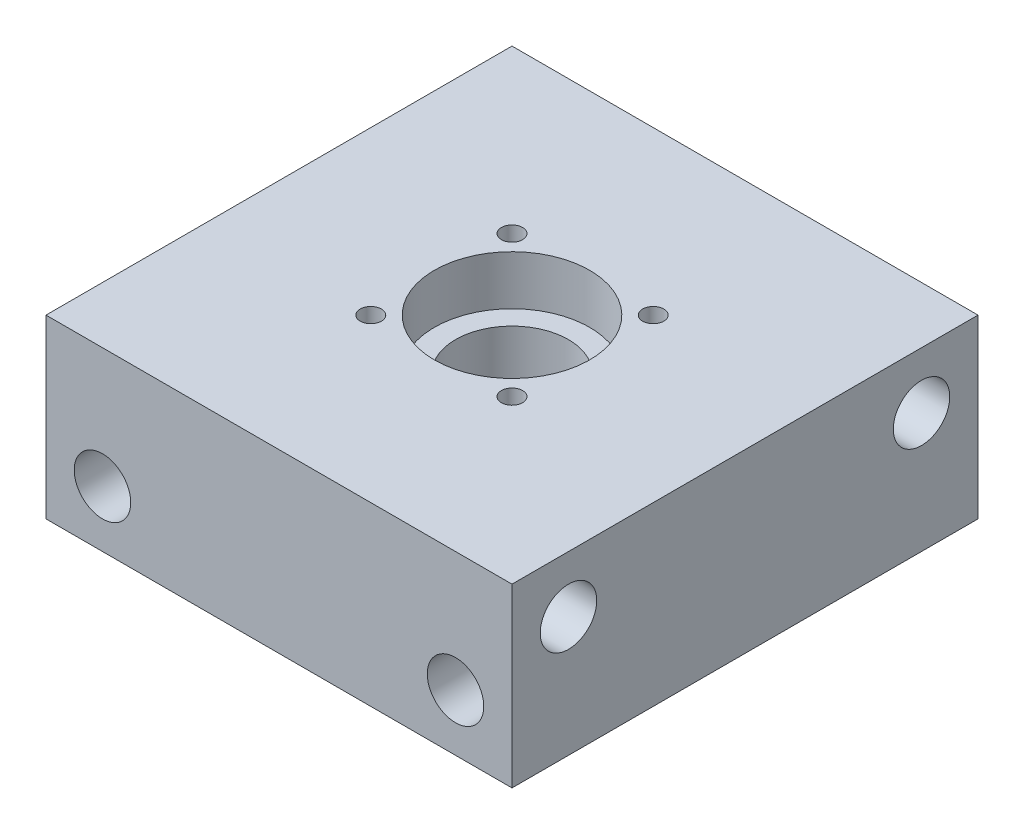
SolidWorks part; units mm, degrees
material "ABS"
ref_plane "Front Plane" through (0, 0, 0) normal (0, 0, 1) x (1, 0, 0)
ref_plane "Top Plane" through (0, 0, 0) normal (0, 1, 0) x (1, 0, 0)
ref_plane "Right Plane" through (0, 0, 0) normal (1, 0, 0) x (0, 0, -1)
sketch "Sketch1" plane through (0, 0, 0) normal (0, 1, 0) x (1, 0, 0)
  line L0 (-25, 94.322) -> (-25, -161.1056) construction
  line L1 (0, 212.1837) -> (0, -209.6879) construction
  line L2 (-178.557, 25) -> (189.3494, 25) construction
  line L3 (-284.8586, 0) -> (271.277, 0) construction
  line L4 (-33, 29) -> (33, 29)
  line L5 (-29, 33) -> (-21, 33)
  line L6 (-29, 33) -> (-29, -33)
  line L7 (-29, -33) -> (-21, -33)
  line L8 (-21, 33) -> (-21, -33)
  line L9 (-33, 21) -> (33, 21)
  line L10 (-33, -29) -> (-33, -21)
  line L11 (-178.557, -25) -> (189.3494, -25) construction
  line L12 (33, -29) -> (33, -21)
  line L13 (-33, 29) -> (33, 29)
  line L14 (-33, 29) -> (-33, 21)
  line L15 (-33, 21) -> (33, 21)
  line L16 (33, 29) -> (33, 21)
  line L17 (-33, -21) -> (33, -21)
  line L18 (-33, -29) -> (33, -29)
  line L19 (-33, -21) -> (33, -21)
  line L20 (-33, -29) -> (33, -29)
  line L21 (29, -33) -> (21, -33)
  line L22 (29, 33) -> (21, 33)
  line L23 (25, 94.322) -> (25, -161.1056) construction
  line L24 (21, 33) -> (21, -33)
  line L25 (29, 33) -> (29, -33)
  line L26 (13.2332, 10) -> (11.6166, 12.8)
  line L27 (-33, 33) -> (33, 33)
  line L28 (-33, 33) -> (-33, -33)
  line L29 (-33, -33) -> (33, -33)
  line L30 (33, 33) -> (33, -33)
  line L31 (-6.7668, 10) -> (-8.3834, 12.8)
  line L32 (-8.3834, 12.8) -> (-11.6166, 12.8)
  line L33 (-11.6166, 12.8) -> (-13.2332, 10)
  line L34 (-13.2332, 10) -> (-11.6166, 7.2)
  line L35 (-11.6166, 7.2) -> (-8.3834, 7.2)
  line L36 (-8.3834, 7.2) -> (-6.7668, 10)
  line L37 (11.6166, 12.8) -> (8.3834, 12.8)
  line L38 (8.3834, 12.8) -> (6.7668, 10)
  line L39 (6.7668, 10) -> (8.3834, 7.2)
  line L40 (8.3834, 7.2) -> (11.6166, 7.2)
  line L41 (11.6166, 7.2) -> (13.2332, 10)
  line L42 (13.2332, -10) -> (11.6166, -7.2)
  line L43 (11.6166, -7.2) -> (8.3834, -7.2)
  line L44 (8.3834, -7.2) -> (6.7668, -10)
  line L45 (6.7668, -10) -> (8.3834, -12.8)
  line L46 (8.3834, -12.8) -> (11.6166, -12.8)
  line L47 (11.6166, -12.8) -> (13.2332, -10)
  line L48 (-6.7668, -10) -> (-8.3834, -7.2)
  line L49 (-8.3834, -7.2) -> (-11.6166, -7.2)
  line L50 (-11.6166, -7.2) -> (-13.2332, -10)
  line L51 (-13.2332, -10) -> (-11.6166, -12.8)
  line L52 (-11.6166, -12.8) -> (-8.3834, -12.8)
  line L53 (-8.3834, -12.8) -> (-6.7668, -10)
  circle A0 centre (0, 0) radius 11
  circle A1 centre (0, 0) radius 8
  circle A2 centre (-10, 10) radius 1.5
  circle A3 centre (10, 10) radius 1.5
  circle A4 centre (10, 10) radius 2.8 construction
  circle A5 centre (10, -10) radius 1.5
  circle A6 centre (-10, 10) radius 2.8 construction
  circle A7 centre (10, -10) radius 2.8 construction
  circle A8 centre (-10, -10) radius 1.5
  circle A9 centre (-10, -10) radius 2.8 construction
  dimension "D5" = 2
  dimension "D6" = 2
  dimension "D7" = 3
  dimension "D14" = 5.6
  dimension "D2" = 25
  dimension "D3" = 25
  dimension "D4" = 4
  dimension "D8" = 10
  dimension "D9" = 10
  dimension "D12" = 8
  dimension "D13" = 4
extrude "Boss-Extrude1" add sketch "Sketch1" along normal blind 25 contours L24 L9 L8 L17 A3 A2 A0 | L24 L4 L8 L9 | L6 L9 L8 L4 | L27 L8 L4 L24 | L8 L5 L6 L4 | L27 L28 L4 L6 | L4 L14 L9 L6 | L9 L28 L17 L6 | L6 L17 L8 L9 | L6 L18 L8 L17 | L10 L18 L6 L17 | L28 L29 L6 L18 | L18 L6 L7 L8 | L24 L17 L8 L18 | L8 L29 L24 L18 | L25 L20 L24 L21 | L25 L19 L24 L20 | L17 L25 L18 L12 | L30 L18 L25 L29 | L25 L15 L24 L19 | L30 L9 L25 L17 | L25 L13 L24 L15 | L4 L25 L9 L16 | L25 L22 L24 L13 | L30 L27 L25 L4 | L35 L36 L31 L32 L33 L34 A2 | L40 L41 L26 L37 L38 L39 A3 | L46 L47 L42 L43 L44 L45 A5 | L52 L53 L48 L49 L50 L51 A8 region at (-31, 0, -31) region at (-31, 0, -25) region at (-25, 0, -31) region at (-25, 0, -25) region at (-31, 0, 0) region at (0, 0, -31) region at (0, 0, -25) region at (-25, 0, 0) region at (-31, 0, 25) region at (25, 0, -31) region at (25, 0, -25) region at (0, 0, -20.406) region at (-25, 0, 25) region at (-31, 0, 31) region at (31, 0, -31) region at (31, 0, -25) region at (25, 0, 0) region at (0, 0, 25) region at (-25, 0, 31) region at (31, 0, 0) region at (25, 0, 25) region at (0, 0, 31) region at (31, 0, 25) region at (25, 0, 31) region at (31, 0, 31) region at (12.3508, 0, -8.6428) region at (-7.6492, 0, -8.6428) region at (12.3508, 0, 11.3572) region at (-7.6492, 0, 11.3572)
extrude "Boss-Extrude2" add sketch "Sketch1<4>" along normal blind 18 contours A0 A1 region at (-10.6889, 0, 0)
sketch "Sketch1<4>" plane through (0, 0, 0) normal (0, 1, 0) x (1, 0, 0) same geometry as "Sketch1"
sketch "Sketch2" plane through (-33, 0, 0) normal (-1, 0, 0) x (0, 0, 1)
  line L0 (0, 0) -> (0, 25) construction
  line L1 (-33, 25) -> (33, 25) construction
  circle A0 centre (-25, 17) radius 4
  circle A1 centre (25, 17) radius 4
  dimension "D3" = 8
  dimension "D1" = 25
  dimension "D2" = 8
extrude "Cut-Extrude1" cut sketch "Sketch2" against normal through all
sketch "Sketch3" plane through (0, 0, -33) normal (0, 0, -1) x (-1, 0, 0)
  line L0 (0, 0) -> (0, 25) construction
  line L1 (33, 25) -> (-33, 25) construction
  line L2 (33, 0) -> (-33, 0) construction
  circle A0 centre (-25, 8) radius 4
  circle A1 centre (25, 8) radius 4
  dimension "D1" = 8
  dimension "D2" = 25
  dimension "D3" = 8
extrude "Cut-Extrude2" cut sketch "Sketch3" against normal through all
extrude "Cut-Extrude3" cut sketch "Sketch1<5>" along normal blind 16.833 contours L52 L53 L48 L49 L50 L51 A8 | L35 L36 L31 L32 L33 L34 A2 | L40 L41 L26 L37 L38 L39 A3 | L46 L47 L42 L43 L44 L45 A5 region at (12.3508, 0, -8.6428) region at (-7.6492, 0, -8.6428) region at (12.3508, 0, 11.3572) region at (-7.6492, 0, 11.3572)
sketch "Sketch1<5>" plane through (0, 0, 0) normal (0, 1, 0) x (1, 0, 0) same geometry as "Sketch1"
equation "\"rod_diameter\"= 8"
equation "\"rod_hole_thickness\"= 4"
equation "\"rod_radius\"= \"rod_diameter\" / 2"
equation "\"platter_diameter\"= 320"
equation "\"platter_radius\"= \"platter_diameter\" / 2"
equation "\"extruder_mount_hole_spacing\"= 75"
equation "\"arm_rod_spacing\"= 40"
equation "\"top_frame_rod_spacing\"= \"arm_rod_spacing\" + 40"
equation "\"motor_level_rod_spacing\"= 15"
equation "\"linear_bearing_diameter\"= 15"
equation "\"z_rod_spacing\"= 75"
equation "\"platter_rod_spacing\"= 50"
equation "\"rod_nut_thickness\"= 6.5"
equation "\"rod_nut_inscribed_diameter\"= 13"
equation "\"D2@Sketch1\"=\"platter_rod_spacing\"/2"
equation "\"D3@Sketch1\"=\"platter_rod_spacing\"/2"
equation "\"D12@Sketch1\"=\"rod_diameter\""
equation "\"D4@Sketch1\"=\"rod_hole_thickness\""
equation "\"D13@Sketch1\"=\"rod_hole_thickness\""
equation "\"D1@Boss-Extrude1\"= \"rod_diameter\" * 2 + \"rod_hole_thickness\" * 2 + 1"
equation "\"D1@Boss-Extrude2\"= \"D1@Boss-Extrude1\" - 7"
equation "\"D1@Sketch2\"=\"platter_rod_spacing\"/2"
equation "\"D2@Sketch2\"=\"rod_radius\"+\"rod_hole_thickness\""
equation "\"D3@Sketch2\"=\"rod_diameter\""
equation "\"D1@Sketch3\"=\"rod_diameter\""
equation "\"D2@Sketch3\"=\"platter_rod_spacing\"/2"
equation "\"D3@Sketch3\"=\"rod_radius\"+\"rod_hole_thickness\""
equation "\"top_frame_spacing\"= 90"
equation "\"z_drive_rod_offset\"= 12"
equation "\"z_height\"= 350"
equation "\"gear_pitch\"=2"
equation "\"r_gear_teeth\"= 450"
equation "\"theta_gear_teeth\"= 385"
equation "\"sheet_thickness\"=5.333"
equation "\"sheet_tab_hole_thickness\"= \"sheet_thickness\""
equation "\"sheet_tab_width\"= \"sheet_thickness\"*2"
equation "\"sheet_double_tab_width\"= 35"
equation "\"sheet_bolt_diameter\"= 3"
equation "\"sheet_bolt_length\"= 16"
equation "\"sheet_nut_diameter\"= 5.5"
equation "\"sheet_nut_thickness\"= 2.5"
equation "\"sheet_nut_depth\"= 10"
equation "\"bearing_outside_diameter\"= 22"
equation "\"bearing_thickness\"= 7"
equation "\"corner_part_thickness\"= \"sheet_thickness\" + \"bearing_thickness\""
equation "\"setscrew_nut_diameter\"= 6"
equation "\"setscrew_nut_thickness\"= 3"
equation "\"setscrew_bolt_diameter\"= 3"
equation "\"motor_shaft_diameter\"= 5.7"
equation "\"D1@Cut-Extrude3\"= \"D1@Boss-Extrude1\" - \"sheet_bolt_length\" + \"sheet_nut_thickness\" + \"sheet_thickness\""
